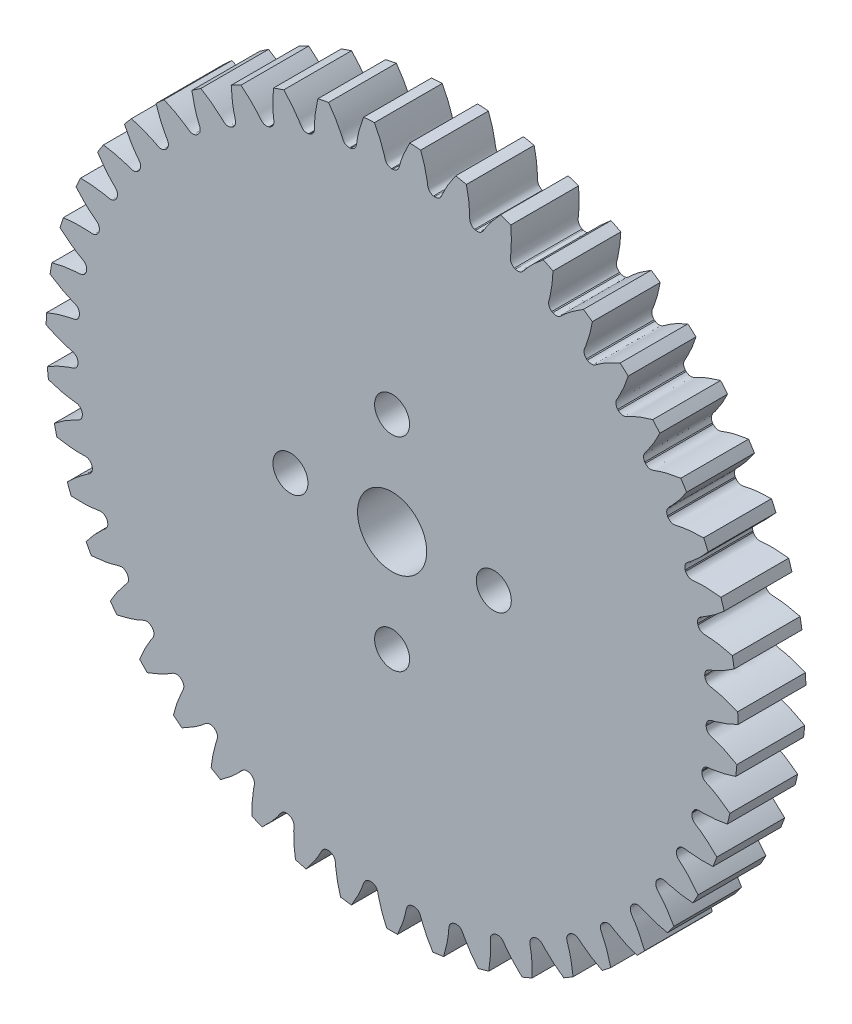
SolidWorks part; units mm, degrees
ref_plane "前视基准面" through (0, 0, 0) normal (0, 0, 1) x (1, 0, 0)
ref_plane "上视基准面" through (0, 0, 0) normal (0, 1, 0) x (1, 0, 0)
ref_plane "右视基准面" through (0, 0, 0) normal (1, 0, 0) x (0, 0, -1)
other "Configuration Table"
sketch "草图1" plane through (0, 0, 0) normal (0, 0, 1) x (1, 0, 0)
  circle A0 centre (0, 0) radius 30.625
ref_axis "基准轴1" through (0, 0, -33.6875) along (0, 0, 1)
sketch "草图2" plane through (0, 0, 0) normal (0, 0, 1) x (1, 0, 0)
  line L0 (0, 0) -> (0, 30.625) construction
  circle A0 centre (0, 0) radius 30.625 construction
  arc A1 (0.0481, 27.8125) -> (-0.0481, 27.8125) centre (0, 0) ccw
  arc A2 (4.7553, 34.6892) -> (-4.7553, 34.6892) centre (0, 0) ccw
  spline S0 degree 3 poles (0.0481, 27.8125) (0.5498, 27.8789) (0.61, 28.2542) (0.7328, 28.6621) (0.7815, 28.8148) (0.8369, 28.977) (0.8993, 29.1484) (0.9691, 29.3288) (1.0467, 29.5179) (1.1324, 29.7157) (1.2267, 29.9217) (1.3298, 30.1357) (1.4422, 30.3575) (1.5642, 30.5867) (1.6962, 30.8231) (1.8384, 31.0664) (1.9912, 31.3162) (2.155, 31.5721) (2.3299, 31.8339) (2.5164, 32.1013) (2.7146, 32.3738) (2.925, 32.651) (3.1477, 32.9327) (3.383, 33.2183) (3.6312, 33.5076) (3.8924, 33.8001) (4.2635, 34.1993) (4.5547, 34.494) (4.7553, 34.6892) knots 0 0 0 0 0.114836 0.132525 0.151522 0.171827 0.193441 0.216363 0.240594 0.266134 0.292982 0.321138 0.350603 0.381377 0.413459 0.446849 0.481548 0.517556 0.554872 0.593496 0.633429 0.674671 0.717221 0.76108 0.806247 0.852722 0.900506 1 1 1 1
  spline S1 degree 3 poles (-0.0481, 27.8125) (-0.5498, 27.8789) (-0.61, 28.2542) (-0.7328, 28.6621) (-0.7815, 28.8148) (-0.8369, 28.977) (-0.8993, 29.1484) (-0.9691, 29.3288) (-1.0467, 29.5179) (-1.1324, 29.7157) (-1.2267, 29.9217) (-1.3298, 30.1357) (-1.4422, 30.3575) (-1.5642, 30.5867) (-1.6962, 30.8231) (-1.8384, 31.0664) (-1.9912, 31.3162) (-2.155, 31.5721) (-2.3299, 31.8339) (-2.5164, 32.1013) (-2.7146, 32.3738) (-2.925, 32.651) (-3.1477, 32.9327) (-3.383, 33.2183) (-3.6312, 33.5076) (-3.8924, 33.8001) (-4.2635, 34.1993) (-4.5547, 34.494) (-4.7553, 34.6892) knots 0 0 0 0 0.114836 0.132525 0.151522 0.171827 0.193441 0.216363 0.240594 0.266134 0.292982 0.321138 0.350603 0.381377 0.413459 0.446849 0.481548 0.517556 0.554872 0.593496 0.633429 0.674671 0.717221 0.76108 0.806247 0.852722 0.900506 1 1 1 1
extrude "凸台-拉伸1" add sketch "草图1" along normal blind 6
extrude "切除-拉伸1" cut sketch "草图2" along normal blind 6
pattern_circular "阵列(圆周)1" count 47 every 7.66 about axis through (0, 0, -33.6875) along (0, 0, 1) of "切除-拉伸1"
sketch "草图3" plane through (0, 0, 0) normal (0, 0, 1) x (1, 0, 0)
  circle A0 centre (0, 0) radius 29.375 construction
  dimension "Dn" = 58.75
sketch "草图4" plane through (0, 0, 6) normal (0, 0, 1) x (1, 0, 0)
  circle A0 centre (0, 0) radius 9 construction
  circle A1 centre (0, 9) radius 1.55
  circle A2 centre (9, 0) radius 1.55
  circle A3 centre (0, 0) radius 9 construction
  circle A4 centre (0, -9) radius 1.55
  circle A5 centre (0, 0) radius 9 construction
  circle A6 centre (-9, 0) radius 1.55
  circle A7 centre (0, 0) radius 9 construction
  circle A8 centre (0, 0) radius 3.06
  point P17 (0, 0)
  dimension "D1" = 18
  dimension "D2" = 3.1
  dimension "D4" = 6.12
  dimension "D3" = 4
extrude "切除-拉伸2" cut sketch "草图4" against normal blind 6
